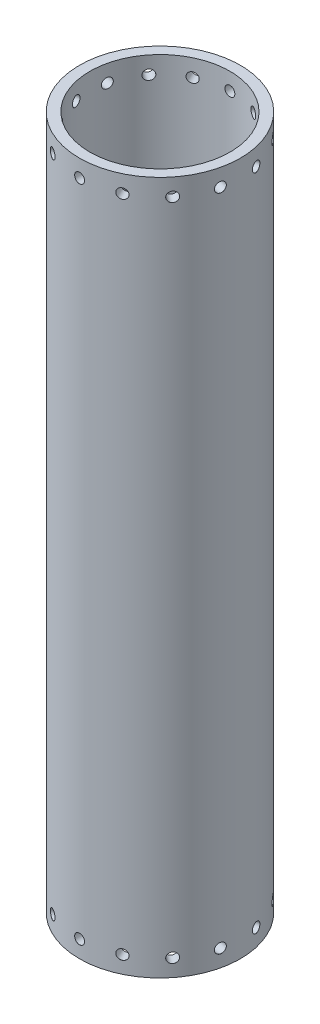
SolidWorks part; units mm, degrees
material "6061-T6 (SS)"
ref_plane "Front Plane" through (0, 0, 0) normal (0, 0, 1) x (1, 0, 0)
ref_plane "Top Plane" through (0, 0, 0) normal (0, 1, 0) x (1, 0, 0)
ref_plane "Right Plane" through (0, 0, 0) normal (1, 0, 0) x (0, 0, -1)
sketch "PipeSketch" plane through (0, 0, 0) normal (0, 1, 0) x (1, 0, 0)
  circle A0 centre (0, 0) radius 38.71
  circle A1 centre (0, 0) radius 44.45
  dimension "OuterDiameter" = 88.9
  dimension "InnerDiameter" = 77.42
extrude "Extrusion" add sketch "PipeSketch" along normal mid plane 383
sketch "FilterSketch" plane through (0, 191.5, 0) normal (0, 1, 0) x (1, 0, 0)
  circle A0 centre (0, 0) radius 38.1
  dimension "NominalDiameter" = 76.2
hole_wizard "M5 Clearance Hole1" positions "3DSketch1" profile "Sketch2" hole size "M5" standard "ISO" end condition up to next
sketch3d "3DSketch1"
  point P147 (0, -182, -44.45)
  dimension "D1" = 9.5
sketch "Sketch2" plane through (0, -182, -44.45) normal (1, 0, 0) x (0, 1, 0)
  line L0 (0, 0) -> (0, 5.74)
  line L1 (0, 5.74) -> (2.75, 5.74)
  line L2 (2.75, 5.74) -> (2.75, 0.025)
  line L3 (2.75, 0.025) -> (2.775, 0)
  line L5 (2.775, 0) -> (0, 0)
  line L6 (-2.75, 0.025) -> (-2.775, 0) construction
  line L11 (0, -6.35) -> (0, 107.95) construction
  dimension "Thru Hole Dia." = 5.5
  dimension "Thru Hole Depth" = 5.74
  dimension "Near C'Sink Dia." = 5.55
  dimension "Near C'Sink Angle" = 90
pattern_circular "CirPattern1" count 14 over 360 about axis through (0, 191.5, 0) along (0, -1, 0) of "M5 Clearance Hole1" reverse direction yes
mirror "Mirror1" about plane through (0, 0, 0) normal (0, 1, 0) of "CirPattern1"
